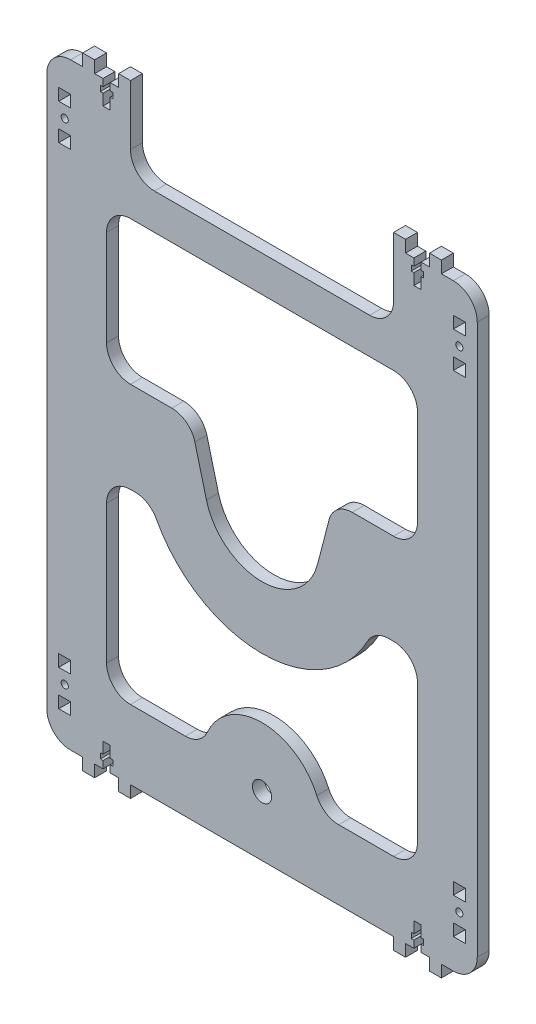
SolidWorks part; units mm, degrees
ref_plane "Front Plane" through (0, 0, 0) normal (0, 0, 1) x (1, 0, 0)
ref_plane "Top Plane" through (0, 0, 0) normal (0, 1, 0) x (1, 0, 0)
ref_plane "Right Plane" through (0, 0, 0) normal (1, 0, 0) x (0, 0, -1)
sketch "Sketch1" plane through (0, 0, 0) normal (0, 0, 1) x (1, 0, 0)
  line L0 (0, 0) -> (187.0096, 0) construction
  line L1 (-90, 125) -> (-55, 125) construction
  line L2 (-90, 125) -> (-90, -125)
  line L3 (-90, -125) -> (90, -125)
  line L4 (90, 125) -> (90, -125)
  line L5 (0, 0) -> (0, 134.5508) construction
  line L6 (-23.2273, -6.0409) -> (-30, 20)
  line L7 (-65, 80) -> (65, 80)
  line L8 (65, 80) -> (65, 0) construction
  line L9 (65, 0) -> (-65, 0) construction
  line L10 (-65, 0) -> (-65, 80) construction
  line L11 (-65, 0) -> (-20, 0) construction
  line L12 (20, 0) -> (65, 0) construction
  line L13 (82.5, 125) -> (82.5, -125) construction
  line L14 (0, 0) -> (0, -125) construction
  line L21 (-30, 20) -> (-65, 20)
  line L22 (-65, 20) -> (-65, 80)
  line L23 (65, 20) -> (65, 80)
  line L24 (30, 20) -> (65, 20)
  line L26 (-90, 125) -> (-55, 125)
  line L27 (23.2273, -6.0409) -> (30, 20)
  line L28 (-55, 125) -> (-55, 95)
  line L29 (-55, 95) -> (55, 95)
  line L30 (55, 95) -> (55, 125)
  line L31 (55, 125) -> (90, 125) construction
  line L32 (55, 125) -> (90, 125)
  line L33 (-46.616, -18.0816) -> (-65, -18.0816)
  line L34 (-65, -18.0816) -> (-65, -95.958)
  line L35 (-65, -95.958) -> (-24.6711, -95.958)
  line L36 (46.616, -18.0816) -> (65, -18.0816)
  line L37 (65, -18.0816) -> (65, -95.958)
  line L38 (65, -95.958) -> (24.6711, -95.958)
  circle A1 centre (0, -100) radius 4
  circle A2 centre (0, 0) radius 24 construction
  arc A3 (23.2273, -6.0409) -> (-23.2273, -6.0409) centre (0, 0) cw
  circle A4 centre (0, 0) radius 50 construction
  circle A5 centre (0, -100) radius 25 construction
  arc A6 (24.6711, -95.958) -> (-24.6711, -95.958) centre (0, -100) ccw
  arc A7 (-46.616, -18.0816) -> (46.616, -18.0816) centre (0, 0) ccw
  line B0 (82.5, 107.5) -> (82.5, 97.5) construction
  line B1 (80, 107.5) -> (80, 112.5)
  line B2 (80, 107.5) -> (85, 107.5)
  line B3 (85, 107.5) -> (85, 112.5)
  line B4 (80, 112.5) -> (85, 112.5)
  line B5 (80, 97.5) -> (80, 92.5)
  line B6 (80, 97.5) -> (85, 97.5)
  line B7 (85, 97.5) -> (85, 92.5)
  line B8 (80, 92.5) -> (85, 92.5)
  line B9 (82.5, 102.5) -> (75.5276, 102.5) construction
  circle B10 centre (82.5, 102.5) radius 1.5
  line B11 (82.5, -107.5) -> (82.5, -97.5) construction
  line B12 (80, -107.5) -> (80, -112.5)
  line B13 (80, -107.5) -> (85, -107.5)
  line B14 (85, -107.5) -> (85, -112.5)
  line B15 (80, -112.5) -> (85, -112.5)
  line B16 (80, -97.5) -> (80, -92.5)
  line B17 (80, -97.5) -> (85, -97.5)
  line B18 (85, -97.5) -> (85, -92.5)
  line B19 (80, -92.5) -> (85, -92.5)
  line B20 (82.5, -102.5) -> (75.5276, -102.5) construction
  circle B21 centre (82.5, -102.5) radius 1.5
  line B22 (-82.5, 107.5) -> (-82.5, 97.5) construction
  line B23 (-80, 107.5) -> (-80, 112.5)
  line B24 (-80, 107.5) -> (-85, 107.5)
  line B25 (-85, 107.5) -> (-85, 112.5)
  line B26 (-80, 112.5) -> (-85, 112.5)
  line B27 (-80, 97.5) -> (-80, 92.5)
  line B28 (-80, 97.5) -> (-85, 97.5)
  line B29 (-85, 97.5) -> (-85, 92.5)
  line B30 (-80, 92.5) -> (-85, 92.5)
  line B31 (-82.5, 102.5) -> (-75.5276, 102.5) construction
  circle B32 centre (-82.5, 102.5) radius 1.5
  line B33 (-82.5, -107.5) -> (-82.5, -97.5) construction
  line B34 (-80, -107.5) -> (-80, -112.5)
  line B35 (-80, -107.5) -> (-85, -107.5)
  line B36 (-85, -107.5) -> (-85, -112.5)
  line B37 (-80, -112.5) -> (-85, -112.5)
  line B38 (-80, -97.5) -> (-80, -92.5)
  line B39 (-80, -97.5) -> (-85, -97.5)
  line B40 (-85, -97.5) -> (-85, -92.5)
  line B41 (-80, -92.5) -> (-85, -92.5)
  line B42 (-82.5, -102.5) -> (-75.5276, -102.5) construction
  circle B43 centre (-82.5, -102.5) radius 1.5
  line B44 (-67.6, -122) -> (-67.6, -119.7)
  line B45 (-63.5, -119.7) -> (-63.5, -115)
  line B46 (-66.5, -115) -> (-66.5, -119.7)
  line B47 (-67.6, -119.7) -> (-66.5, -119.7)
  line B48 (-65, -125) -> (-65, -113.7792) construction
  line B49 (-66.5, -125) -> (-70, -125)
  line B50 (-70, -130) -> (-75, -130)
  line B51 (-75, -130) -> (-75, -125)
  line B52 (-70, -130) -> (-70, -125)
  line B53 (-63.5, -125) -> (-60, -125)
  line B54 (-60, -125) -> (-60, -130)
  line B55 (-60, -130) -> (-55, -130)
  line B56 (-55, -130) -> (-55, -125)
  line B57 (-66.5, -125) -> (-63.5, -125) construction
  line B58 (-63.5, -125) -> (-63.5, -122)
  line B59 (-63.5, -119.7) -> (-62.4, -119.7)
  line B60 (-62.4, -122) -> (-63.5, -122)
  line B61 (-63.5, -115) -> (-66.5, -115)
  line B62 (-66.5, -122) -> (-67.6, -122)
  line B63 (-62.4, -119.7) -> (-62.4, -122)
  line B64 (-66.5, -122) -> (-66.5, -125)
  line B65 (-65, -115) -> (-65, -125) construction
  line B66 (62.4, -122) -> (62.4, -119.7)
  line B67 (66.5, -119.7) -> (66.5, -115)
  line B68 (63.5, -115) -> (63.5, -119.7)
  line B69 (62.4, -119.7) -> (63.5, -119.7)
  line B70 (65, -125) -> (65, -113.7792) construction
  line B71 (63.5, -125) -> (60, -125)
  line B72 (60, -130) -> (55, -130)
  line B73 (55, -130) -> (55, -125)
  line B74 (60, -130) -> (60, -125)
  line B75 (66.5, -125) -> (70, -125)
  line B76 (70, -125) -> (70, -130)
  line B77 (70, -130) -> (75, -130)
  line B78 (75, -130) -> (75, -125)
  line B79 (63.5, -125) -> (66.5, -125) construction
  line B80 (66.5, -125) -> (66.5, -122)
  line B81 (66.5, -119.7) -> (67.6, -119.7)
  line B82 (67.6, -122) -> (66.5, -122)
  line B83 (66.5, -115) -> (63.5, -115)
  line B84 (63.5, -122) -> (62.4, -122)
  line B85 (67.6, -119.7) -> (67.6, -122)
  line B86 (63.5, -122) -> (63.5, -125)
  line B87 (65, -115) -> (65, -125) construction
  line B88 (67.6, 122) -> (67.6, 119.7)
  line B89 (63.5, 119.7) -> (63.5, 115)
  line B90 (66.5, 115) -> (66.5, 119.7)
  line B91 (67.6, 119.7) -> (66.5, 119.7)
  line B92 (65, 125) -> (65, 113.7792) construction
  line B93 (66.5, 125) -> (70, 125)
  line B94 (70, 130) -> (75, 130)
  line B95 (75, 130) -> (75, 125)
  line B96 (70, 130) -> (70, 125)
  line B97 (63.5, 125) -> (60, 125)
  line B98 (60, 125) -> (60, 130)
  line B99 (60, 130) -> (55, 130)
  line B100 (55, 130) -> (55, 125)
  line B101 (66.5, 125) -> (63.5, 125) construction
  line B102 (63.5, 125) -> (63.5, 122)
  line B103 (63.5, 119.7) -> (62.4, 119.7)
  line B104 (62.4, 122) -> (63.5, 122)
  line B105 (63.5, 115) -> (66.5, 115)
  line B106 (66.5, 122) -> (67.6, 122)
  line B107 (62.4, 119.7) -> (62.4, 122)
  line B108 (66.5, 122) -> (66.5, 125)
  line B109 (65, 115) -> (65, 125) construction
  line B110 (-62.4, 122) -> (-62.4, 119.7)
  line B111 (-66.5, 119.7) -> (-66.5, 115)
  line B112 (-63.5, 115) -> (-63.5, 119.7)
  line B113 (-62.4, 119.7) -> (-63.5, 119.7)
  line B114 (-65, 125) -> (-65, 113.7792) construction
  line B115 (-63.5, 125) -> (-60, 125)
  line B116 (-60, 130) -> (-55, 130)
  line B117 (-55, 130) -> (-55, 125)
  line B118 (-60, 130) -> (-60, 125)
  line B119 (-66.5, 125) -> (-70, 125)
  line B120 (-70, 125) -> (-70, 130)
  line B121 (-70, 130) -> (-75, 130)
  line B122 (-75, 130) -> (-75, 125)
  line B123 (-63.5, 125) -> (-66.5, 125) construction
  line B124 (-66.5, 125) -> (-66.5, 122)
  line B125 (-66.5, 119.7) -> (-67.6, 119.7)
  line B126 (-67.6, 122) -> (-66.5, 122)
  line B127 (-66.5, 115) -> (-63.5, 115)
  line B128 (-63.5, 122) -> (-62.4, 122)
  line B129 (-67.6, 119.7) -> (-67.6, 122)
  line B130 (-63.5, 122) -> (-63.5, 125)
  line B131 (-65, 115) -> (-65, 125) construction
  dimension "D8" = 50
  dimension "D10" = 8
  dimension "D2" = 24
  dimension "D13" = 100
  dimension "D3" = 250
  dimension "D4" = 180
  dimension "D5" = 35
  dimension "D6" = 25
  dimension "D7" = 20
  dimension "D9" = 22.5
  dimension "D11" = 25
  dimension "D12" = 7.5
  dimension "D14" = 15
  dimension "D15" = 30
sketch_block_instance "Trou M3 plots 5mm-7"
sketch_block "Trou M3 plots 5mm" parameters "D2"=3, "D1"=5, "D3"=5, "D4"=10
sketch_block_instance "Trou M3 plots 5mm-8"
sketch_block_instance "Trou M3 plots 5mm-9"
sketch_block_instance "Trou M3 plots 5mm-10"
sketch_block_instance "Insert M3 plots ep 5mm-1"
sketch_block "Insert M3 plots ep 5mm" parameters "D1"=10, "D2"=5, "D3"=5
sketch_block_instance "Decoupe Insert M3-4"
sketch_block "Decoupe Insert M3" parameters "D1"=5.2, "D2"=3, "D3"=2.3, "D4"=3, "D5"=10
sketch_block_instance "Insert M3 plots ep 5mm-2"
sketch_block_instance "Insert M3 plots ep 5mm-3"
sketch_block_instance "Insert M3 plots ep 5mm-5"
extrude "Boss-Extrude1" add sketch "Sketch1" along normal blind 5 contours B130 B128 B110 B113 B112 B127 B111 B125 B129 B126 B124 L26 L2 L3 B64 B62 B44 B47 B46 B61 B45 B59 B63 B60 B58 B86 B84 B66 B69 B68 B83 B67 B81 B85 B82 B80 L4 | B50 B52 L3 B51 | B55 B56 L3 B54 | B72 B74 L3 B73 | B77 B78 L3 B76 | B121 B122 L26 B120 | B116 B118 L26 B117 | B99 B100 L26 B98 | B94 B96 L26 B95 region at (-82.5, 121.9194, 0) region at (-72.5, 127.5, 0) region at (-72.5, -127.5, 0) region at (-57.5, 127.5, 0) region at (-57.5, -127.5, 0) region at (57.5, -127.5, 0) region at (57.5, 127.5, 0) region at (72.5, -127.5, 0) region at (72.5, 127.5, 0)
fillet "Fillet1" radius 10 20 edges at (-90, -125, 2.5) (90, -125, 2.5) (-90, 125, 2.5) (90, 125, 2.5) (-55, 95, 2.5) (55, 95, 2.5) (24.6711, -95.958, 2.5) (-24.6711, -95.958, 2.5) (-65, -95.958, 2.5) (65, -95.958, 2.5) (65, -18.0816, 2.5) (46.616, -18.0816, 2.5) (-46.616, -18.0816, 2.5) (-65, -18.0816, 2.5) (65, 80, 2.5) (-65, 80, 2.5) (65, 20, 2.5) (-65, 20, 2.5) (30, 20, 2.5) (-30, 20, 2.5)
